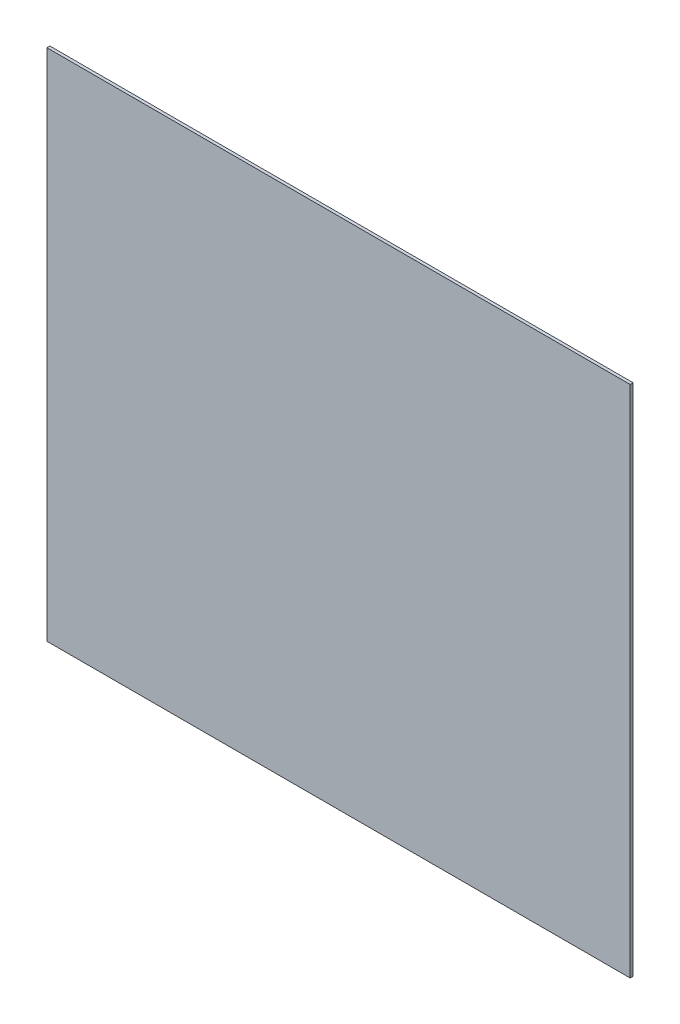
SolidWorks part; units mm, degrees
ref_plane "前视基准面" through (0, 0, 0) normal (0, 0, 1) x (1, 0, 0)
ref_plane "上视基准面" through (0, 0, 0) normal (0, 1, 0) x (1, 0, 0)
ref_plane "右视基准面" through (0, 0, 0) normal (1, 0, 0) x (0, 0, -1)
sketch "草图1" plane through (0, 0, 0) normal (0, 0, 1) x (1, 0, 0)
  line L1 (-147.5, -130) -> (147.5, -130)
  line L2 (-147.5, -130) -> (-147.5, 130)
  line L3 (-147.5, 130) -> (147.5, 130)
  line L4 (147.5, -130) -> (147.5, 130)
  line L5 (-147.5, -130) -> (147.5, 130) construction
  line L6 (-147.5, 130) -> (147.5, -130) construction
  point P0 (0, 0)
  dimension "D1" = 295
  dimension "D2" = 260
base flange "基体-法兰1" sketch "草图1" thickness 1.5 reverse thickness direction no parameters "D1"=0.7366
sketch "折弯-线1" plane through (0, 0, 0) normal (0, 1, 0) x (1, 0, 0)
sketch "边界框1" plane through (0, 0, 0) normal (0, 1, 0) x (1, 0, 0)
sheet metal parameters "钣金6" thickness 1.5 parameters "D1"=0.7366
flat pattern "平板型式6" [suppressed]
sketch "折弯-线2" plane through (0, 0, 0) normal (0, 1, 0) x (1, 0, 0)
sketch "边界框2" [suppressed] plane through (0, 0, 0) normal (0, 1, 0) x (1, 0, 0)
